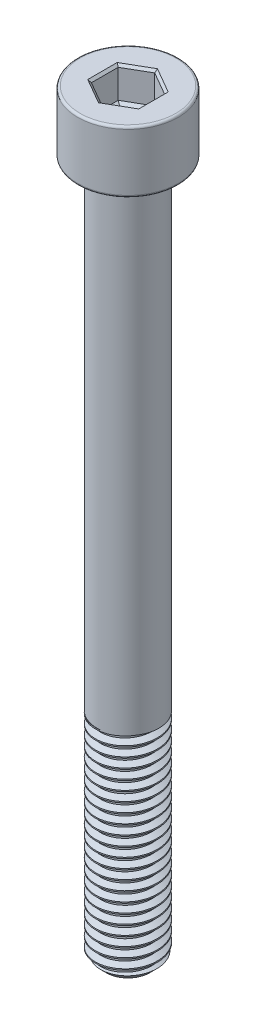
SolidWorks part; units mm, degrees
material "AISI Type A2 Tool Steel"
ref_plane "Front Plane" through (0, 0, 0) normal (0, 0, 1) x (1, 0, 0)
ref_plane "Top Plane" through (0, 0, 0) normal (0, 1, 0) x (1, 0, 0)
ref_plane "Right Plane" through (0, 0, 0) normal (1, 0, 0) x (0, 0, -1)
sketch "Sketch1" plane through (0, 0, 0) normal (0, 1, 0) x (1, 0, 0)
  circle A0 centre (0, 0) radius 4
  dimension "D1" = 8
extrude "Boss-Extrude1" add sketch "Sketch1" along normal blind 28
thread "Thread1" pitch 1.25 method cut profile "Thread Profile1" start angle 0, offset 2, length 0, pitch 1.25, diameter 8
ref_plane "Plane1" through (-4, 30, 0) normal (0, 0, 1) x (-1, 0, 0)
sketch "Thread Profile1" plane through (-4, 30, 0) normal (0, 0, 1) x (-1, 0, 0)
  line L0 (0, 0) -> (0, 1.25) construction
  line L11 (0, 0) -> (0, 1.0937)
  line L12 (0, 1.0937) -> (-0.6766, 0.7031)
  line L13 (-0.6766, 0.7031) -> (-0.6766, 0.3906)
  line L15 (-0.6766, 0.3906) -> (0, 0)
  line L17 (-0.6766, 0.5469) -> (0, 0.5469) construction
  point P2 (0, 0)
  dimension "Pitch" = 1.25
  dimension "Profile_Angle" = 60
  dimension "Profile_Land" = 0.3125
  dimension "Profile_Height" = 0.6766
sketch "Sketch2" plane through (0, 28, 0) normal (0, 1, 0) x (1, 0, 0)
  circle A0 centre (0, 0) radius 4
  dimension "D1" = 8
extrude "Boss-Extrude2" add sketch "Sketch2" along normal blind 62
sketch "Sketch5" plane through (0, 90, 0) normal (0, 1, 0) x (1, 0, 0)
  circle A0 centre (0, 0) radius 6.5
  dimension "D1" = 13
extrude "Boss-Extrude3" add sketch "Sketch5" along normal blind 8
sketch "Sketch6" plane through (0, 0, 0) normal (0, 0, 1) x (1, 0, 0)
  line L0 (0, 0) -> (0, 0.7245) construction
  line L1 (0, 0) -> (4.01, 0) construction
  line L2 (4.01, 0) -> (4.01, 1.2)
  line L3 (4.01, 1.2) -> (2.81, 0)
  line L4 (2.81, 0) -> (4.01, 0)
  dimension "D1" = 1.2
  dimension "D2" = 45
  dimension "D3" = 4.01
revolve "Cut-Revolve1" cut sketch "Sketch6" angle 360 about L0
fillet "Fillet1" radius 0.3 2 edges at (0, 90, 6.5) (0, 98, 6.5)
sketch "Sketch7" plane through (0, 98, 0) normal (0, 1, 0) x (1, 0, 0)
  line L1 (0, 3.4641) -> (-3, 1.7321)
  line L2 (-3, 1.7321) -> (-3, -1.7321)
  line L3 (-3, -1.7321) -> (0, -3.4641)
  line L4 (0, -3.4641) -> (3, -1.7321)
  line L5 (3, -1.7321) -> (3, 1.7321)
  line L6 (3, 1.7321) -> (0, 3.4641)
  circle A0 centre (0, 0) radius 3 construction
  dimension "D1" = 6
extrude "Cut-Extrude1" cut sketch "Sketch7" against normal blind 4
chamfer "Chamfer1" distance 0.3 angle 45 6 edges at (-3, 98, 0) (-1.5, 98, 2.5981) (1.5, 98, 2.5981) (3, 98, 0) (1.5, 98, -2.5981) (-1.5, 98, -2.5981)
sketch "Sketch8" plane through (0, 94, 0) normal (0, 1, 0) x (1, 0, 0)
  line L1 (0, 3.4641) -> (-3, 1.7321)
  line L2 (-3, 1.7321) -> (-3, -1.7321)
  line L3 (-3, -1.7321) -> (0, -3.4641)
  line L4 (0, -3.4641) -> (3, -1.7321)
  line L5 (3, -1.7321) -> (3, 1.7321)
  line L6 (3, 1.7321) -> (0, 3.4641)
  circle A0 centre (0, 0) radius 3 construction
extrude "Cut-Extrude2" cut sketch "Sketch8" against normal blind 0.4 draft 60
